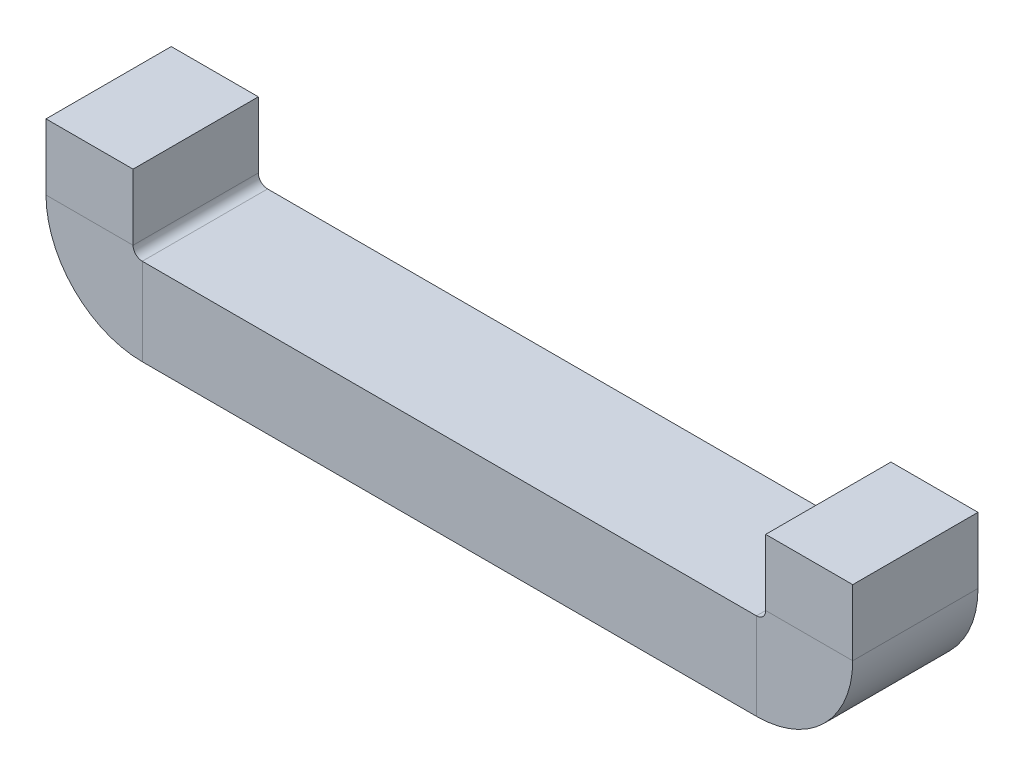
SolidWorks part; units mm, degrees
note: The reader was unsure of these and kept them because the rebuilt part matched: flange length of "Ребро-кромка1".
material "Латунь"
ref_plane "Спереди" through (0, 0, 0) normal (0, 0, 1) x (1, 0, 0)
ref_plane "Сверху" through (0, 0, 0) normal (0, 1, 0) x (1, 0, 0)
ref_plane "Справа" through (0, 0, 0) normal (1, 0, 0) x (0, 0, -1)
other "Configuration Table"
sketch "Эскиз2" plane through (0, 0, 0) normal (0, 1, 0) x (1, 0, 0)
  line L1 (25.25, 5) -> (-25.25, 5)
  line L2 (25.25, 5) -> (25.25, -5)
  line L3 (25.25, -5) -> (-25.25, -5)
  line L4 (-25.25, 5) -> (-25.25, -5)
  line L5 (25.25, 5) -> (-25.25, -5) construction
  line L6 (25.25, -5) -> (-25.25, 5) construction
  point P0 (0, 0)
  dimension "D1" = 10
  dimension "D2" = 50.5
base flange "Базовая кромка1" sketch "Эскиз2" thickness 6.95 reverse thickness direction no parameters "D1"=0.7366
edge flange "Ребро-кромка1" sketch "Эскиз11" flange profiles "Эскиз11", "Эскиз12" flange angle 90 flange length 6 flange position material outside bend radius 0.7366 thickness 6.95 relief rectangular parameters "D6"=10, "D8"=1
sketch "Эскиз11" plane through (-25.25, 0, 0) normal (-1, 0, 0) x (0, 0, 1)
  line L2 (-5, 0) -> (-5, 6)
  line L3 (-5, 6) -> (5, 6)
  line L4 (5, 6) -> (5, 0)
  line L7 (-5, 0) -> (5, 0) construction
  line L8 (-5, 0) -> (5, 0)
sketch "Эскиз12" plane through (25.25, 0, 0) normal (1, 0, 0) x (0, 0, -1)
  line L2 (-5, 0) -> (-5, 6)
  line L3 (-5, 6) -> (5, 6)
  line L4 (5, 6) -> (5, 0)
  line L7 (-5, 0) -> (5, 0) construction
  line L8 (-5, 0) -> (5, 0)
bend "EdgeBend1" bend radius 0.7366 bend angle 90 parameters "D5"=1
bend "EdgeBend2" bend radius 0.7366 bend angle 90 parameters "D5"=2
sketch "Bend-Lines1" [suppressed] plane through (0, 0, 0) normal (0, 1, 0) x (1, 0, 0)
sketch "Bounding-Box1" [suppressed] plane through (0, 0, 0) normal (0, 1, 0) x (1, 0, 0)
sheet metal parameters "Sheet-Metal3" thickness 6.95 parameters "D1"=0.7366
flat pattern "Flat-Pattern3" [suppressed]
sketch "Bend-Lines2" plane through (0, 0, 0) normal (0, 1, 0) x (1, 0, 0)
sketch "Bounding-Box2" [suppressed] plane through (0, 0, 0) normal (0, 1, 0) x (1, 0, 0)
sheet metal parameters "Sheet-Metal4" thickness 6.95 parameters "D1"=0.7366
flat pattern "Flat-Pattern3"
sketch "Bend-Lines2" plane through (0, 0, 0) normal (0, 1, 0) x (1, 0, 0)
  line L0 (27.8212, -5) -> (27.8212, 5) construction
  line L1 (-27.8212, 5) -> (-27.8212, -5) construction
  line L2 (27.8212, -5) -> (27.8212, 5) construction
  line L3 (-27.8212, 5) -> (-27.8212, -5) construction
sketch3d "Bounding-Box2" [suppressed]
  line L0 (36.3924, 5, 0) -> (-36.3924, 5, 0) construction
  line L1 (36.3924, -5, 0) -> (-36.3924, -5, 0) construction
  line L2 (36.3924, 5, 0) -> (36.3924, -5, 0) construction
  line L3 (-36.3924, 5, 0) -> (-36.3924, -5, 0) construction
bend of the flat pattern "Плоское состояние-<EdgeBend1>1"
bend of the flat pattern "Плоское состояние-<EdgeBend2>1"
